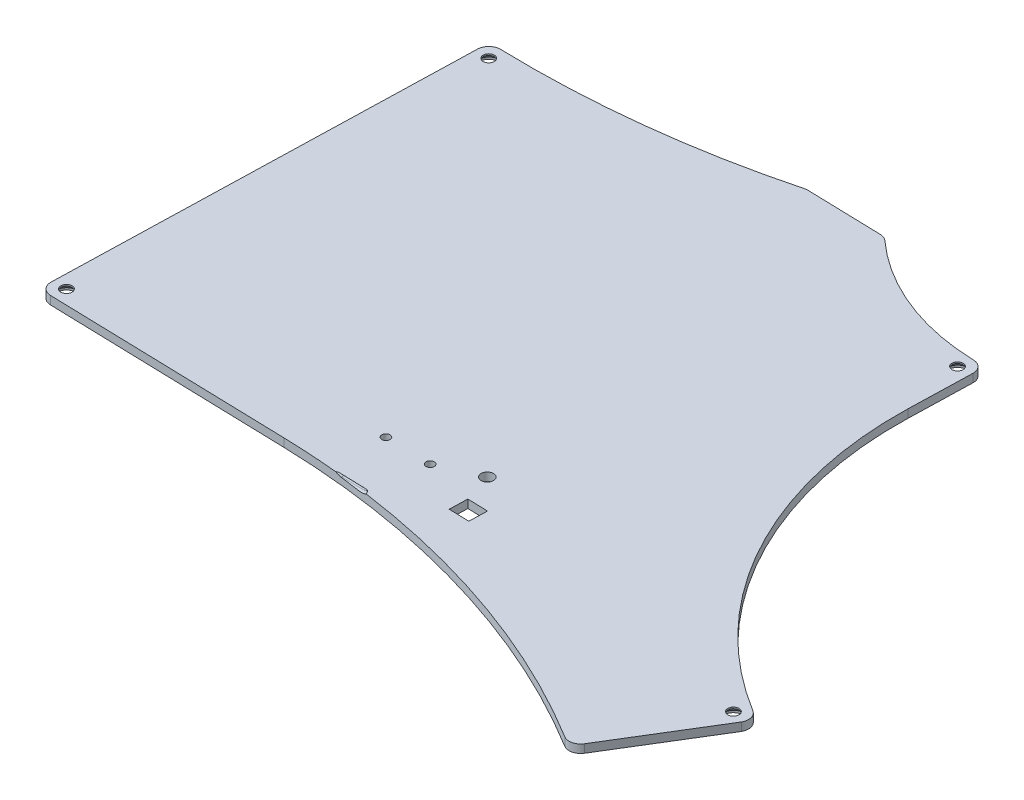
SolidWorks part; units mm, degrees
ref_plane "Front Plane" through (0, 0, 0) normal (0, 0, 1) x (1, 0, 0)
ref_plane "Top Plane" through (0, 0, 0) normal (0, 1, 0) x (1, 0, 0)
ref_plane "Right Plane" through (0, 0, 0) normal (1, 0, 0) x (0, 0, -1)
sketch "Main" plane through (0, 0, 0) normal (0, 1, 0) x (1, 0, 0)
  line L13 (-10.5797, -88.3991) -> (-6.2814, -88.5178) construction
  line L18 (-10.8741, -88.1909) -> (-5.976, -88.3262) construction
  line L19 (-10.8741, -88.1909) -> (-10.9955, -92.5892) construction
  line L20 (-5.976, -88.3262) -> (-6.0974, -92.7245) construction
  line L21 (-10.9955, -92.5892) -> (-6.0974, -92.7245) construction
  line L22 (-10.7873, -92.2949) -> (-10.6824, -88.4963) construction
  line L23 (-6.1842, -88.6205) -> (-6.2891, -92.4191) construction
  line L26 (-6.3918, -92.5163) -> (-10.6901, -92.3976) construction
  line L69 (-104.2231, 7.3223) -> (-106.9973, -93.1394)
  line L70 (-16.4114, 17.4022) -> (-34.4046, 17.899)
  line L71 (23.6817, -16.0031) -> (24.1037, -0.7231)
  line L72 (54.716, -125.4699) -> (69.1643, -101.872)
  line L73 (-104.0813, -96.2211) -> (-45.8908, -97.828)
  line L74 (-104.2231, 7.3223) -> (-106.9973, -93.1394) construction
  line L75 (-16.4114, 17.4022) -> (-34.4046, 17.899) construction
  line L76 (23.6817, -16.0031) -> (24.1037, -0.7231) construction
  line L77 (54.716, -125.4699) -> (69.1643, -101.872) construction
  line L78 (-104.0813, -96.2211) -> (-45.8908, -97.828) construction
  circle A11 centre (-13.1327, -81.2259) radius 1.5 construction
  circle A19 centre (-13.1327, -81.2259) radius 1.5 construction
  circle A24 centre (65.8328, -100.6104) radius 1.35 construction
  circle A25 centre (-103.4848, -92.7362) radius 1.35 construction
  circle A26 centre (-100.7383, 6.7264) radius 1.35 construction
  circle A27 centre (20.5913, -1.1242) radius 1.35 construction
  circle A28 centre (-100.7383, 6.7264) radius 1.35 construction
  circle A125 centre (-22.7527, -85.442) radius 1 construction
  circle A126 centre (-33.7485, -85.1383) radius 1 construction
  arc A135 (-106.9973, -93.1394) -> (-104.0813, -96.2211) centre (-103.9985, -93.2222) ccw
  arc A136 (-101.1415, 10.2383) -> (-104.2231, 7.3223) centre (-101.2243, 7.2395) ccw
  arc A137 (-101.1415, 10.2383) -> (-35.2476, 17.8023) centre (-94.6684, 244.649) ccw
  arc A138 (-34.4046, 17.899) -> (-35.2476, 17.8023) centre (-34.4874, 14.9002) ccw
  arc A139 (-14.4856, 16.6317) -> (-16.4114, 17.4022) centre (-16.4942, 14.4033) ccw
  arc A140 (-14.4856, 16.6317) -> (21.1876, 2.3586) centre (22.7216, 57.9088) ccw
  arc A141 (24.1037, -0.7231) -> (21.1876, 2.3586) centre (21.1048, -0.6403) ccw
  arc A142 (23.6817, -16.0031) -> (68.0862, -97.8876) centre (116.6499, -18.5703) ccw
  arc A143 (69.1643, -101.872) -> (68.0862, -97.8876) centre (66.5172, -100.4502) ccw
  arc A144 (50.591, -126.4619) -> (54.716, -125.4699) centre (52.1575, -123.9034) ccw
  arc A145 (50.591, -126.4619) -> (-45.8908, -97.828) centre (-51.2758, -292.8371) ccw
  arc A146 (-106.9973, -93.1394) -> (-104.0813, -96.2211) centre (-103.9985, -93.2222) ccw construction
  arc A147 (-101.1415, 10.2383) -> (-104.2231, 7.3223) centre (-101.2243, 7.2395) ccw construction
  arc A148 (-101.1415, 10.2383) -> (-35.2476, 17.8023) centre (-94.6684, 244.649) ccw construction
  arc A149 (-34.4046, 17.899) -> (-35.2476, 17.8023) centre (-34.4874, 14.9002) ccw construction
  arc A150 (-14.4856, 16.6317) -> (-16.4114, 17.4022) centre (-16.4942, 14.4033) ccw construction
  arc A151 (-14.4856, 16.6317) -> (21.1876, 2.3586) centre (22.7216, 57.9088) ccw construction
  arc A152 (24.1037, -0.7231) -> (21.1876, 2.3586) centre (21.1048, -0.6403) ccw construction
  arc A153 (23.6817, -16.0031) -> (68.0862, -97.8876) centre (116.6499, -18.5703) ccw construction
  arc A154 (69.1643, -101.872) -> (68.0862, -97.8876) centre (66.5172, -100.4502) ccw construction
  arc A155 (50.591, -126.4619) -> (54.716, -125.4699) centre (52.1575, -123.9034) ccw construction
  arc A156 (50.591, -126.4619) -> (-45.8908, -97.828) centre (-51.2758, -292.8371) ccw construction
  dimension "D2" = 3
  dimension "D3" = 2
  dimension "D4" = 0.2
  dimension "D5" = 0.2
  dimension "D6" = 0.2
  dimension "D7" = 0.2
  dimension "D1" = 0
sketch "Sketch7" plane through (0, 0, 0) normal (0, 1, 0) x (1, 0, 0)
  line L0 (-10.8741, -88.1909) -> (-5.976, -88.3262)
  line L1 (-5.976, -88.3262) -> (-6.0974, -92.7245)
  line L2 (-6.0974, -92.7245) -> (-10.9955, -92.5892)
  line L3 (-10.9955, -92.5892) -> (-10.8741, -88.1909)
  line L42 (-104.0232, 7.3167) -> (-106.7974, -93.145)
  line L43 (-104.0757, -96.0212) -> (-45.8853, -97.6281)
  line L44 (54.5454, -125.3654) -> (68.9908, -101.7724)
  line L45 (23.4818, -15.9975) -> (23.9038, -0.7176)
  line L46 (-16.417, 17.2023) -> (-34.4101, 17.6991)
  line L47 (-104.0232, 7.3167) -> (-106.7974, -93.145)
  line L48 (-104.0757, -96.0212) -> (-45.8853, -97.6281)
  line L49 (54.5454, -125.3654) -> (68.9908, -101.7724)
  line L50 (23.4818, -15.9975) -> (23.9038, -0.7176)
  line L51 (-16.417, 17.2023) -> (-34.4101, 17.6991)
  circle A0 centre (-33.7485, -85.1383) radius 1
  circle A1 centre (-22.7527, -85.442) radius 1
  circle A2 centre (-13.1327, -81.2259) radius 1.5
  circle A3 centre (-33.7485, -85.1383) radius 1 construction
  circle A4 centre (-13.1327, -81.2259) radius 1.5 construction
  circle A5 centre (-103.4848, -92.7362) radius 1.35
  circle A6 centre (-100.7383, 6.7264) radius 1.35
  circle A7 centre (20.5913, -1.1242) radius 1.35
  circle A8 centre (65.8328, -100.6104) radius 1.35
  circle A9 centre (65.8328, -100.6104) radius 1.35 construction
  arc A110 (-101.147, 10.0384) -> (-104.0232, 7.3167) centre (-101.2243, 7.2395) ccw
  arc A111 (-106.7974, -93.145) -> (-104.0757, -96.0212) centre (-103.9985, -93.2222) ccw
  arc A112 (50.6954, -126.2913) -> (-45.8853, -97.6281) centre (-51.2758, -292.8371) ccw
  arc A113 (50.6954, -126.2913) -> (54.5454, -125.3654) centre (52.1575, -123.9034) ccw
  arc A114 (68.9908, -101.7724) -> (67.9817, -98.0582) centre (66.5172, -100.4502) ccw
  arc A115 (23.4818, -15.9975) -> (67.9817, -98.0582) centre (116.6499, -18.5703) ccw
  arc A116 (23.9038, -0.7176) -> (21.1821, 2.1586) centre (21.1048, -0.6403) ccw
  arc A117 (-14.6195, 16.4831) -> (21.1821, 2.1586) centre (22.7216, 57.9088) ccw
  arc A118 (-14.6195, 16.4831) -> (-16.417, 17.2023) centre (-16.4942, 14.4033) ccw
  arc A119 (-34.4101, 17.6991) -> (-35.1969, 17.6088) centre (-34.4874, 14.9002) ccw
  arc A120 (-101.147, 10.0384) -> (-35.1969, 17.6088) centre (-94.6684, 244.649) ccw
  arc A121 (-101.147, 10.0384) -> (-104.0232, 7.3167) centre (-101.2243, 7.2395) ccw
  arc A122 (-106.7974, -93.145) -> (-104.0757, -96.0212) centre (-103.9985, -93.2222) ccw
  arc A123 (50.6954, -126.2913) -> (-45.8853, -97.6281) centre (-51.2758, -292.8371) ccw
  arc A124 (50.6954, -126.2913) -> (54.5454, -125.3654) centre (52.1575, -123.9034) ccw
  arc A125 (68.9908, -101.7724) -> (67.9817, -98.0582) centre (66.5172, -100.4502) ccw
  arc A126 (23.4818, -15.9975) -> (67.9817, -98.0582) centre (116.6499, -18.5703) ccw
  arc A127 (23.9038, -0.7176) -> (21.1821, 2.1586) centre (21.1048, -0.6403) ccw
  arc A128 (-14.6195, 16.4831) -> (21.1821, 2.1586) centre (22.7216, 57.9088) ccw
  arc A129 (-14.6195, 16.4831) -> (-16.417, 17.2023) centre (-16.4942, 14.4033) ccw
  arc A130 (-34.4101, 17.6991) -> (-35.1969, 17.6088) centre (-34.4874, 14.9002) ccw
  arc A131 (-101.147, 10.0384) -> (-35.1969, 17.6088) centre (-94.6684, 244.649) ccw
  dimension "D1" = 0.2
extrude "Main_plate" add sketch "Sketch7" against normal blind 2
ref_plane "Charge_port_plane1" through (-2.7344, 0, 99.0197) normal (-0.0276, 0, 0.9996) x (0.9996, 0, 0.0276)
ref_plane "Charge_port_plane2" through (-2.8724, 0, 104.0178) normal (-0.0276, 0, 0.9996) x (0.9996, 0, 0.0276)
sketch "Sketch8" plane through (-2.7344, 0, 99.0197) normal (-0.0276, 0, 0.9996) x (0.9996, 0, 0.0276)
  line L0 (-28.2855, 3.5) -> (-23.4855, 3.5) construction
  line L1 (-28.2855, 6.75) -> (-23.4855, 6.75) construction
  line L2 (-28.2855, 0.25) -> (-23.4855, 0.25) construction
  line L3 (-104.1855, -2) -> (-104.1855, 0) construction
  line L4 (-101.3855, -2) -> (-43.1729, -2) construction
  line L5 (-28.2855, 7.25) -> (-23.4855, 7.25)
  line L6 (-28.2855, -0.25) -> (-23.4855, -0.25)
  arc A0 (-28.2855, 6.75) -> (-28.2855, 0.25) centre (-28.2855, 3.5) ccw construction
  arc A1 (-23.4855, 0.25) -> (-23.4855, 6.75) centre (-23.4855, 3.5) ccw construction
  arc A2 (-23.4855, -0.25) -> (-23.4855, 7.25) centre (-23.4855, 3.5) ccw
  arc A3 (-28.2855, 7.25) -> (-28.2855, -0.25) centre (-28.2855, 3.5) ccw
  point P2 (-25.8855, 3.5)
  dimension "D5" = 0.5
  dimension "D1" = 4.8
  dimension "D2" = 6.5
  dimension "D3" = 78.3
  dimension "D4" = 5.5
sketch "Sketch9" plane through (-2.8724, 0, 104.0178) normal (-0.0276, 0, 0.9996) x (0.9996, 0, 0.0276)
  line L4 (-28.2855, -1.75) -> (-23.4855, -1.75)
  line L5 (-23.4855, 8.75) -> (-28.2855, 8.75)
  line L6 (-28.2855, -1.75) -> (-23.4855, -1.75)
  line L7 (-23.4855, 8.75) -> (-28.2855, 8.75)
  arc A4 (-28.2855, 8.75) -> (-28.2855, -1.75) centre (-28.2855, 3.5) ccw
  arc A5 (-23.4855, -1.75) -> (-23.4855, 8.75) centre (-23.4855, 3.5) ccw
  arc A6 (-28.2855, 8.75) -> (-28.2855, -1.75) centre (-28.2855, 3.5) ccw
  arc A7 (-23.4855, -1.75) -> (-23.4855, 8.75) centre (-23.4855, 3.5) ccw
  dimension "D1" = 1.5
loft "Charge_port" cut profiles "Sketch8", "Sketch9"
fillet "Charge_port_fllet" radius 0.3 3 edges
sketch "Sketch10" plane through (0, -2, 0) normal (0, -1, 0) x (1, 0, 0)
  line L0 (-104.0232, -7.3167) -> (-106.7974, 93.145) construction
  circle A0 centre (-103.4848, 92.7362) radius 2.5
  circle A1 centre (65.8328, 100.6104) radius 2.5
  circle A2 centre (20.5913, 1.1242) radius 2.5
  circle A3 centre (-100.7383, -6.7264) radius 2.5
  dimension "D1" = 5
extrude "Screw_holes" cut sketch "Sketch10" against normal blind 1.7
chamfer "Screw_holes_chamfer" distance 1.2 angle 45 4 edges at (65.8328, -0.3, 98.1104) (-103.4848, -0.3, 90.2362) (-100.7383, -0.3, -9.2264) (20.5913, -0.3, -1.3758)
